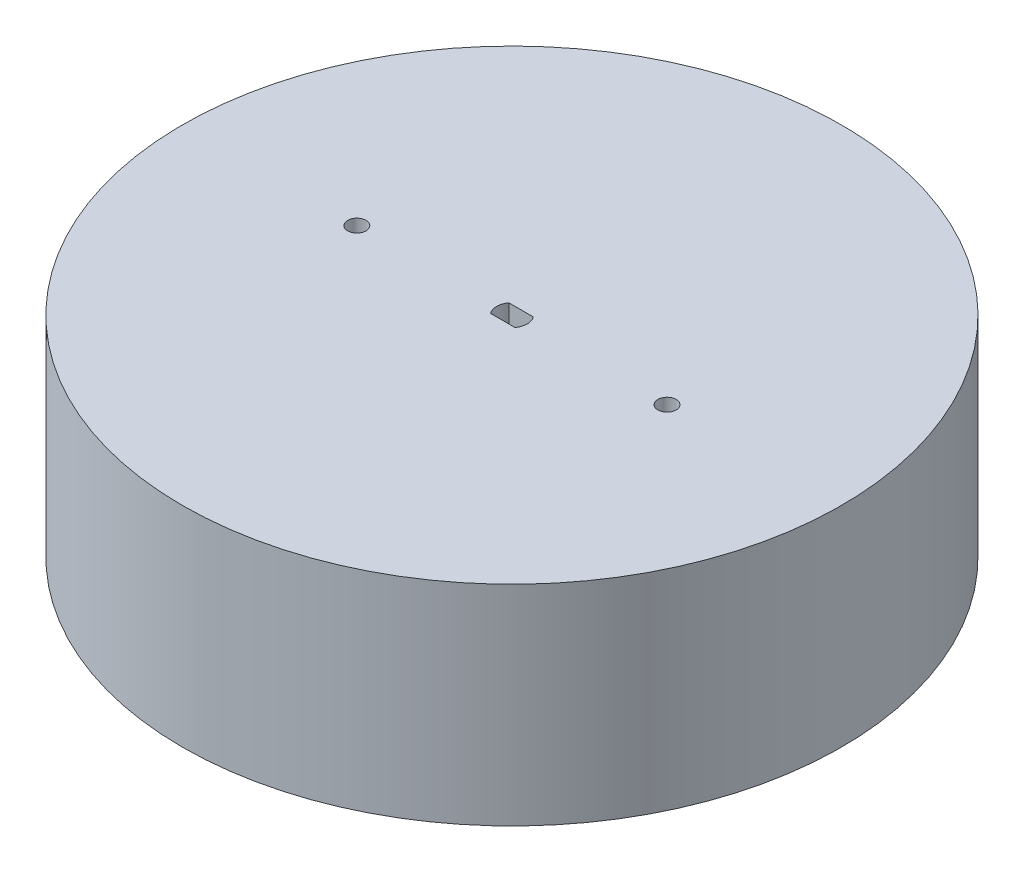
SolidWorks part; units mm, degrees
ref_plane "Front Plane" through (0, 0, 0) normal (0, 0, 1) x (1, 0, 0)
ref_plane "Top Plane" through (0, 0, 0) normal (0, 1, 0) x (1, 0, 0)
ref_plane "Right Plane" through (0, 0, 0) normal (1, 0, 0) x (0, 0, -1)
sketch "Sketch1" plane through (0, 0, 0) normal (0, 1, 0) x (1, 0, 0)
  circle A0 centre (0, 0) radius 47.625
  circle A1 centre (0, 0) radius 53.975
  dimension "D1" = 95.25
  dimension "D2" = 107.95
extrude "Boss-Extrude1" add sketch "Sketch1" along normal blind 8.89 contours A0 | A1 A0 region at (0, 0, 0) region at (-52.4484, 0, 0)
extrude "Boss-Extrude2" add sketch "Sketch1<4>" against normal blind 25.4
sketch "Sketch1<4>" plane through (0, 0, 0) normal (0, 1, 0) x (1, 0, 0) same geometry as "Sketch1"
sketch "Sketch2" plane through (0, 8.89, 0) normal (0, 1, 0) x (1, 0, 0)
  line L0 (-2, 1.5) -> (2, 1.5)
  line L1 (-2, -1.5) -> (2, -1.5)
  arc A0 (2, 1.5) -> (2, -1.5) centre (0, 0) cw
  arc A1 (-2, 1.5) -> (-2, -1.5) centre (0, 0) ccw
extrude "Cut-Extrude1" cut sketch "Sketch2" against normal blind 25.4
sketch "Sketch3" plane through (0, 0, 0) normal (0, -1, 0) x (1, 0, 0)
  circle A0 centre (0, 0) radius 34.925
  circle A1 centre (0, 0) radius 47.625
  circle A2 centre (0, 0) radius 47.625 construction
  dimension "3" = 69.85
extrude "Boss-Extrude3" add sketch "Sketch3" along normal blind 3.4925
sketch "Sketch4" plane through (0, 8.89, 0) normal (0, 1, 0) x (1, 0, 0)
  circle A0 centre (25.4, 0) radius 1.5
  circle A1 centre (-25.4, 0) radius 1.5
  dimension "D1" = 3
  dimension "D2" = 25.4
  dimension "D3" = 25.4
extrude "Cut-Extrude2" cut sketch "Sketch4" against normal blind 21.2725
